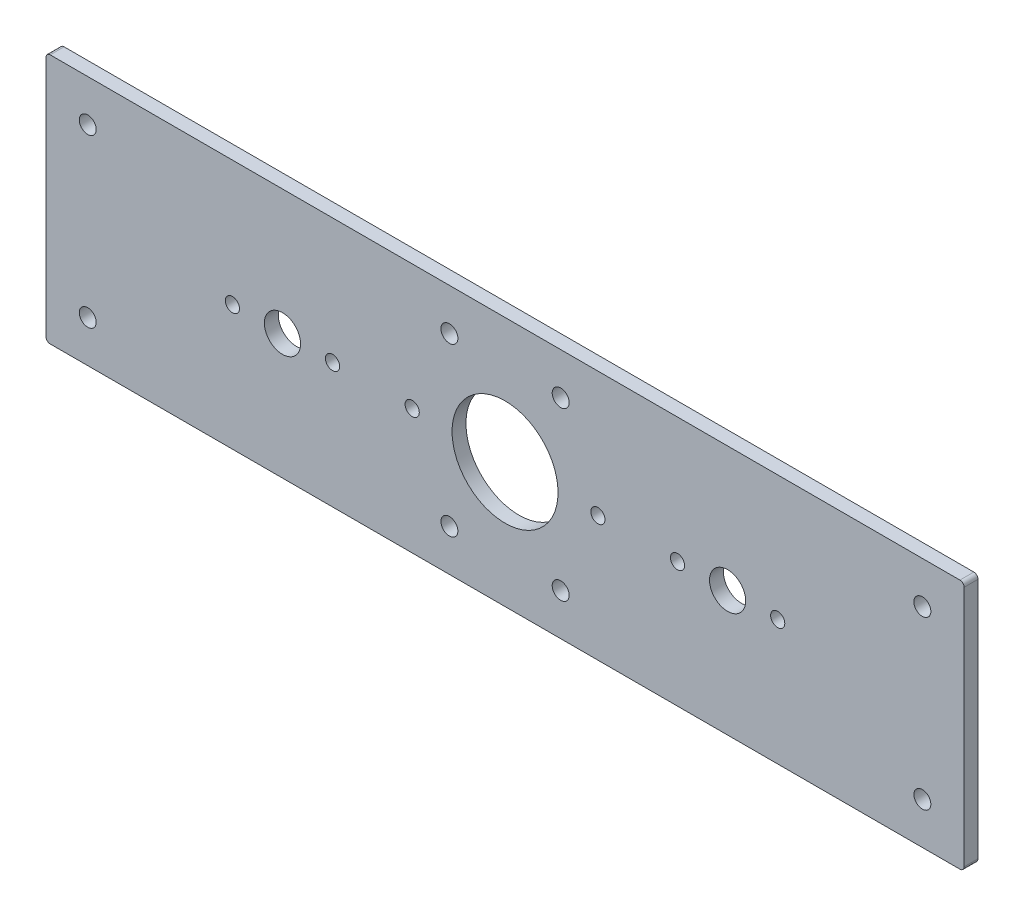
SolidWorks part; units mm, degrees
ref_plane "Front Plane" through (0, 0, 0) normal (0, 0, 1) x (1, 0, 0)
ref_plane "Top Plane" through (0, 0, 0) normal (0, 1, 0) x (1, 0, 0)
ref_plane "Right Plane" through (0, 0, 0) normal (1, 0, 0) x (0, 0, -1)
sketch "Sketch1" plane through (0, 0, 0) normal (0, 0, 1) x (1, 0, 0)
  line L0 (-165, 0) -> (165, 0) construction
  line L1 (165, -45) -> (-165, -45)
  line L2 (165, -45) -> (165, 45)
  line L3 (165, 45) -> (-165, 45)
  line L4 (-165, -45) -> (-165, 45)
  line L5 (165, -45) -> (-165, 45) construction
  line L6 (165, 45) -> (-165, -45) construction
  line L8 (0, -33.3754) -> (33.3754, 0) construction
  line L9 (0, -33.3754) -> (-33.3754, 0) construction
  line L10 (-33.3754, 0) -> (0, 33.3754) construction
  line L11 (33.3754, 0) -> (0, 33.3754) construction
  line L12 (0, -33.3754) -> (0, 33.3754) construction
  line L13 (-33.3754, 0) -> (33.3754, 0) construction
  circle A0 centre (0, 0) radius 19.05
  circle A1 centre (-33.3754, 0) radius 2.55
  circle A2 centre (33.3754, 0) radius 2.55
  point P0 (0, 0)
  dimension "D3" = 38.1
  dimension "D4" = 47.2
  dimension "D5" = 47.2
  dimension "D8" = 5.1
  dimension "D9" = 5.1
  dimension "D1" = 90
  dimension "D2" = 330
  dimension "D6" = 90
  dimension "D7" = 90
extrude "Boss-Extrude1" add sketch "Sketch1" along normal mid plane 5
sketch "Sketch2" plane through (0, 0, 2.5) normal (0, 0, 1) x (1, 0, 0)
  line L2 (-150, 45) -> (-150, -45)
  line L3 (-150, 45) -> (-150, -45) construction
  line L5 (150, -45) -> (150, 45)
  line L6 (150, -45) -> (150, 45) construction
  line L23 (165, 30) -> (-165, 30)
  line L24 (165, 30) -> (-165, 30) construction
  line L25 (0, 45) -> (0, -45) construction
  line L26 (-165, -30) -> (165, -30)
  line L27 (-165, -30) -> (165, -30) construction
  line L28 (165, 45) -> (-165, 45) construction
  line L29 (-165, -45) -> (165, -45) construction
  line L30 (-20, 45) -> (-20, -45) construction
  line L31 (20, 45) -> (20, -45) construction
  circle A0 centre (-150, 30) radius 3.05
  circle A1 centre (-150, -30) radius 3.05
  circle A2 centre (-20, 30) radius 3.05
  circle A3 centre (-20, -30) radius 3.05
  circle A4 centre (20, -30) radius 3.05
  circle A5 centre (20, 30) radius 3.05
  circle A6 centre (150, 30) radius 3.05
  circle A7 centre (150, -30) radius 3.05
  dimension "D7" = 6.1
  dimension "D8" = 6.1
  dimension "D9" = 6.1
  dimension "D10" = 6.1
  dimension "D11" = 6.1
  dimension "D12" = 6.1
  dimension "D13" = 6.1
  dimension "D14" = 6.1
  dimension "D1" = 15
  dimension "D2" = 15
  dimension "D3" = 15
  dimension "D4" = 15
  dimension "D5" = 20
  dimension "D6" = 20
extrude "Cut-Extrude1" cut sketch "Sketch2" against normal through all
sketch "Sketch3" plane through (0, 0, 2.5) normal (0, 0, 1) x (1, 0, 0)
  line L0 (0, 0) -> (-49.4534, 0) construction
  circle A0 centre (-62, 0) radius 2.55
  circle A1 centre (-98, 0) radius 2.55
  circle A2 centre (-80, 0) radius 6.5
  dimension "D1" = 5.1
  dimension "D2" = 5.1
  dimension "D3" = 13
  dimension "D4" = 80
  dimension "D5" = 18
  dimension "D6" = 18
extrude "Cut-Extrude2" cut sketch "Sketch3" against normal through all
mirror "Mirror1" about plane through (0, 0, 0) normal (1, 0, 0) of "Cut-Extrude2"
fillet "Fillet1" radius 1.5 4 edges at (-165, -45, 0) (165, -45, 0) (165, 45, 0) (-165, 45, 0)
equation "\"D4@Sketch3\"=160/2"
equation "\"D9@Sketch2\"=\"D7@Sketch2\""
equation "\"D12@Sketch2\"=\"D7@Sketch2\""
equation "\"D13@Sketch2\"=\"D7@Sketch2\""
equation "\"D8@Sketch2\"=\"D7@Sketch2\""
equation "\"D10@Sketch2\"=\"D7@Sketch2\""
equation "\"D11@Sketch2\"=\"D7@Sketch2\""
equation "\"D14@Sketch2\"=\"D7@Sketch2\""
